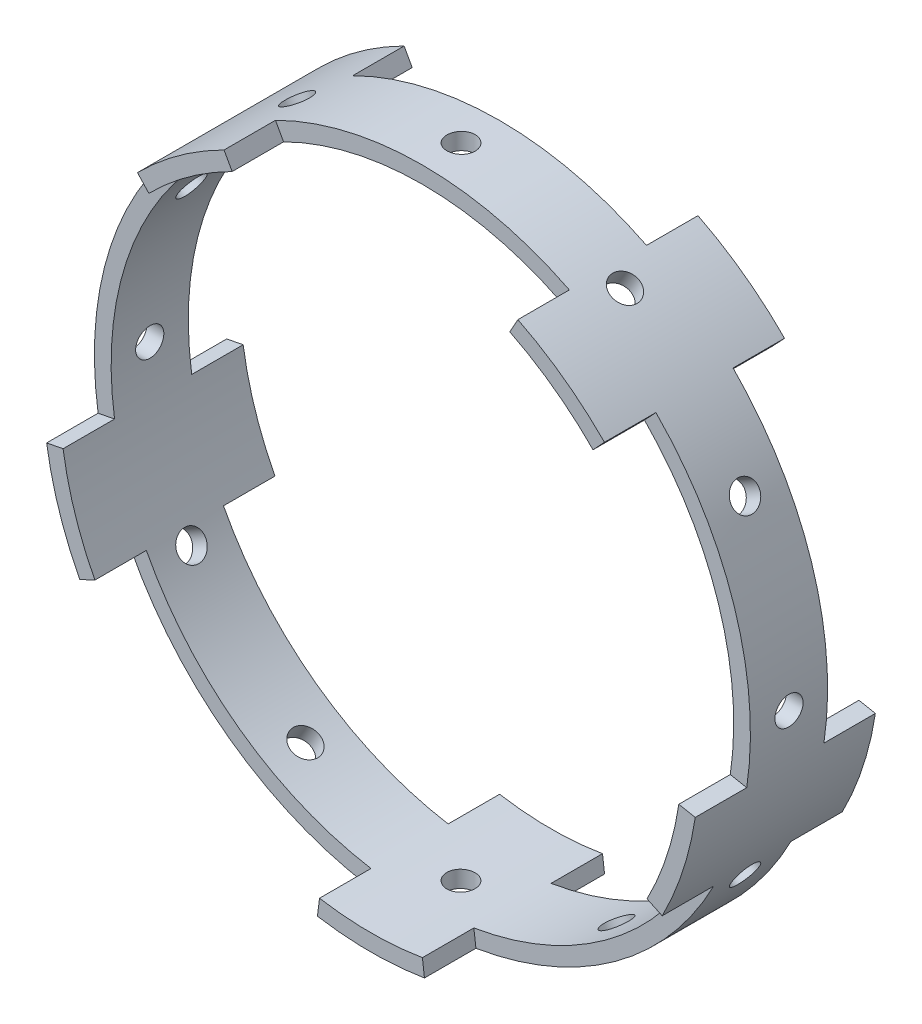
SolidWorks part; units mm, degrees
ref_plane "Front Plane" through (0, 0, 0) normal (0, 0, 1) x (1, 0, 0)
ref_plane "Top Plane" through (0, 0, 0) normal (0, 1, 0) x (1, 0, 0)
ref_plane "Right Plane" through (0, 0, 0) normal (1, 0, 0) x (0, 0, -1)
sketch "Sketch1" plane through (0, 0, 0) normal (0, 0, 1) x (1, 0, 0)
  circle A0 centre (0, 0) radius 76.835
  circle A1 centre (0, 0) radius 80.9625
  dimension "D1" = 153.67
  dimension "D2" = 161.925
extrude "Boss-Extrude1" add sketch "Sketch1" along normal blind 19.05
sketch "Sketch3" plane through (0, 0, 19.05) normal (0, 0, 1) x (1, 0, 0)
  line L0 (-13.208, -79.8779) -> (-12.7, -75.7781)
  line L1 (12.7, -75.7781) -> (13.208, -79.8779)
  line L2 (-68.1448, -35.4952) -> (-71.8869, -37.2452)
  line L3 (-80.0499, -12.1221) -> (-75.9938, -11.3383)
  line L4 (-54.8158, 53.8409) -> (-57.6365, 56.8591)
  line L5 (-36.2655, 72.386) -> (-34.2668, 68.7707)
  line L6 (34.2668, 68.7707) -> (36.2655, 72.386)
  line L7 (57.6365, 56.8591) -> (54.8158, 53.8409)
  line L8 (75.9938, -11.3383) -> (80.0499, -12.1221)
  line L9 (71.8869, -37.2452) -> (68.1448, -35.4952)
  arc A0 (-12.7, -75.7781) -> (12.7, -75.7781) centre (0, 0) ccw
  circle A1 centre (0, 0) radius 76.835 construction
  arc A2 (13.208, -79.8779) -> (-13.208, -79.8779) centre (0, 0) cw
  circle A3 centre (0, 0) radius 80.9625 construction
  arc A4 (-71.8869, -37.2452) -> (-80.0499, -12.1221) centre (0, 0) cw
  arc A5 (-75.9938, -11.3383) -> (-68.1448, -35.4952) centre (0, 0) ccw
  arc A6 (-57.6365, 56.8591) -> (-36.2655, 72.386) centre (0, 0) cw
  arc A7 (-34.2668, 68.7707) -> (-54.8158, 53.8409) centre (0, 0) ccw
  arc A8 (36.2655, 72.386) -> (57.6365, 56.8591) centre (0, 0) cw
  arc A9 (54.8158, 53.8409) -> (34.2668, 68.7707) centre (0, 0) ccw
  arc A10 (80.0499, -12.1221) -> (71.8869, -37.2452) centre (0, 0) cw
  arc A11 (68.1448, -35.4952) -> (75.9938, -11.3383) centre (0, 0) ccw
  point P28 (0, 0)
  dimension "D1" = 12.7
  dimension "D2" = 12.7
  dimension "D3" = 13.208
  dimension "D4" = 13.208
  dimension "D5" = 5
extrude "Boss-Extrude2" add sketch "Sketch3" along normal blind 12.7 and the other way blind 31.75
sketch "Sketch2" plane through (0, 0, 0) normal (0, 1, 0) x (1, 0, 0)
  line L0 (76.835, 0) -> (-76.835, 0) construction
  line L1 (0, -2.0807) -> (0, -15.8358) construction
  circle A0 centre (0, -9.525) radius 3.4782
  dimension "D1" = 9.525
extrude "Cut-Extrude1" cut sketch "Sketch2" against normal through all
ref_axis "Axis1" through (0, 0, 2.0807) along (0, 0, 1)
pattern_circular "CirPattern1" count 12 over 360 about axis through (0, 0, 2.0807) along (0, 0, 1) of "Cut-Extrude1"
